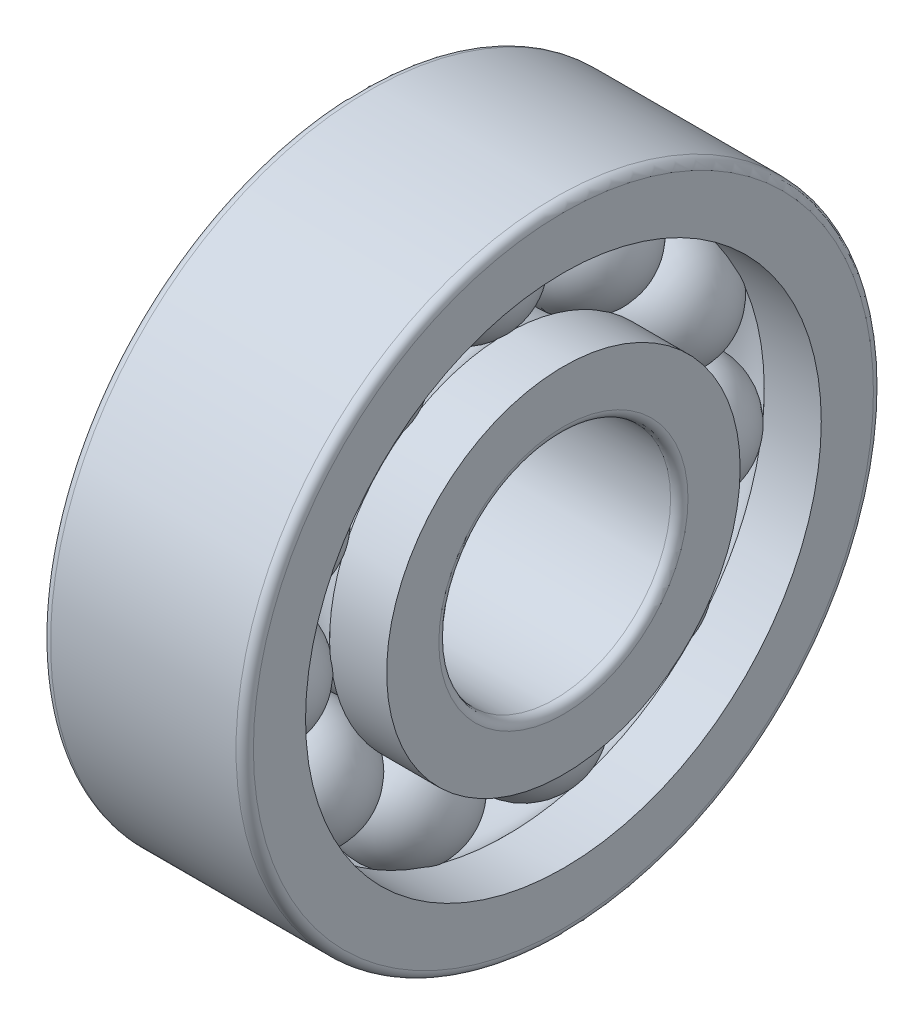
SolidWorks part; units mm, degrees
ref_plane "Plane1" through (0, 0, 0) normal (0, 0, 1) x (1, 0, 0)
ref_plane "Plane2" through (0, 0, 0) normal (0, 1, 0) x (1, 0, 0)
ref_plane "Plane3" through (0, 0, 0) normal (1, 0, 0) x (0, 0, -1)
revolve "InnerRace" add sketch "InnRacSke" angle 360 about L5 reverse direction yes
sketch "InnRacSke" plane through (0, 0, 0) normal (0, 0, 1) x (1, 0, 0)
  line L0 (-1.5315, 6.1) -> (-3.5, 6.1)
  line L1 (-3.5, 6.1) -> (-3.5, 4.3)
  line L2 (-3.2, 4) -> (3.2, 4)
  line L3 (3.5, 4.3) -> (3.5, 6.1)
  line L4 (3.5, 6.1) -> (1.5315, 6.1)
  line L5 (-20.6375, 0) -> (20.6375, 0) construction
  line L6 (0, 0) -> (0, 30) construction
  arc A0 (-3.5, 4.3) -> (-3.2, 4) centre (-3.2, 4.3) ccw
  arc A1 (3.2, 4) -> (3.5, 4.3) centre (3.2, 4.3) ccw
  arc A2 (1.5315, 6.1) -> (-1.5315, 6.1) centre (0, 7.5) cw
  dimension "Fillet_radius" = 0.3
  dimension "Ball_diameter" = 4.15
  dimension "ID" = 8
  dimension "OD" = 12.2
  dimension "Width" = 7
  dimension "BallCLRad" = 7.5
sketch "Clipboard" plane through (0, 0, 0) normal (0, 0, 1) x (1, 0, 0)
  line L0 (-10, 0) -> (10, 0) construction
  line L1 (0, 0) -> (21.9499, -4.2666)
  line L2 (0, 0) -> (7.4989, -0.1309)
  line L3 (0, 0) -> (22.3573, 0.3902)
  line L4 (0, 0) -> (-22.3573, -0.3902)
  dimension "BallCLRad" = 7.5
  dimension "Count" = 359
  dimension "Show_count" = 359
  dimension "Max_count" = 11
  dimension "Min_count" = 1
sketch "CagSpiSke" plane through (0, 0, 0) normal (0, 0, 1) x (1, 0, 0)
  line L0 (0.21, 7.15) -> (0.21, 7.85)
  line L1 (0.21, 7.85) -> (-0.21, 7.85)
  line L2 (-0.21, 7.85) -> (-0.21, 7.15)
  line L3 (-0.21, 7.15) -> (0.21, 7.15)
  line L4 (-20.6375, 0) -> (20.6375, 0) construction
  line L5 (0, 0) -> (0, 23.7692) construction
  dimension "Thickness" = 0.42
  dimension "OD" = 15.7
  dimension "ID" = 14.3
revolve "CageSpine" add sketch "CagSpiSke" angle 0.001 about L4 reverse direction yes
ref_axis "Axis1" through (-50, 0, 0) along (1, 0, 0)
sketch "CagBalSke" plane through (0, 0, 0) normal (0, 0, 1) x (1, 0, 0)
  line L0 (-2.31, 7.5) -> (2.31, 7.5)
  line L1 (-1.905, 7.5) -> (1.905, 7.5) construction
  line L2 (-10, 0) -> (10, 0) construction
  line L3 (0, 0) -> (0, 24) construction
  arc A0 (2.31, 7.5) -> (-2.31, 7.5) centre (0, 7.5) cw
  dimension "CageWallOD" = 4.62
  dimension "BallCLRad" = 7.5
revolve "CageBall" [suppressed] add sketch "CagBalSke" angle 360 about L1 reverse direction yes
pattern_circular "CageBalls" [suppressed] count 11 every 32.727 about axis through (-50, 0, 0) along (1, 0, 0)
sketch "CagTrmODSke" plane through (0, 0, 0) normal (0, 0, 1) x (1, 0, 0)
  line L0 (2.311, 7.85) -> (2.311, 9.811)
  line L1 (2.311, 9.811) -> (-2.311, 9.811)
  line L2 (-2.311, 9.811) -> (-2.311, 7.85)
  line L3 (-2.311, 7.85) -> (2.311, 7.85)
  line L4 (-20.6375, 0) -> (20.6375, 0) construction
  line L5 (0, 0) -> (0, 25) construction
  dimension "Width" = 4.622
  dimension "ID" = 15.7
  dimension "OD" = 19.622
revolve "CageTrimOD" [suppressed] cut sketch "CagTrmODSke" angle 360 about L4 reverse direction yes
sketch "CagTrmIDSke" plane through (0, 0, 0) normal (0, 0, 1) x (1, 0, 0)
  line L0 (2.311, 5.191) -> (2.311, 7.15)
  line L1 (2.311, 7.15) -> (-2.311, 7.15)
  line L2 (-2.311, 7.15) -> (-2.311, 5.191)
  line L3 (-2.311, 5.191) -> (2.311, 5.191)
  line L4 (-20.6375, 0) -> (20.6375, 0) construction
  line L5 (0, 0) -> (0, 25) construction
  dimension "ID" = 10.382
  dimension "OD" = 14.3
  dimension "Width" = 4.622
revolve "CageTrimID" [suppressed] cut sketch "CagTrmIDSke" angle 360 about L4 reverse direction yes
sketch "BalSimSke" plane through (0, 0, 0) normal (0, 0, 1) x (1, 0, 0)
  line L0 (-10, 0) -> (10, 0) construction
  line L1 (-10, 7.5) -> (10, 7.5) construction
  line L2 (0, 0) -> (0, 23) construction
  circle A0 centre (0, 7.5) radius 2.1
  dimension "Ball_diameter" = 4.2
  dimension "BallCLRad" = 7.5
revolve "BallsSimplified" [suppressed] add sketch "BalSimSke" angle 360 about L0
sketch "BalDetSke" plane through (0, 0, 0) normal (0, 0, 1) x (1, 0, 0)
  line L0 (-2.1, 7.5) -> (2.1, 7.5)
  line L1 (-1.905, 7.5) -> (1.905, 7.5) construction
  line L2 (0, 0) -> (0, 25) construction
  arc A0 (2.1, 7.5) -> (-2.1, 7.5) centre (0, 7.5) cw
  dimension "Ball_diameter" = 4.2
  dimension "BallCLRad" = 7.5
revolve "BallDetailed" add sketch "BalDetSke" angle 360 about L1 reverse direction yes
sketch "OutRacSke" plane through (0, 0, 0) normal (0, 0, 1) x (1, 0, 0)
  line L0 (-1.5315, 8.9) -> (-3.5, 8.9)
  line L1 (-3.5, 8.9) -> (-3.5, 10.7)
  line L2 (-3.2, 11) -> (3.2, 11)
  line L3 (3.5, 10.7) -> (3.5, 8.9)
  line L4 (3.5, 8.9) -> (1.5315, 8.9)
  line L5 (-20.6375, 0) -> (20.6375, 0) construction
  line L6 (0, 0) -> (0, 30) construction
  arc A0 (-3.5, 10.7) -> (-3.2, 11) centre (-3.2, 10.7) cw
  arc A1 (3.2, 11) -> (3.5, 10.7) centre (3.2, 10.7) cw
  arc A2 (1.5315, 8.9) -> (-1.5315, 8.9) centre (0, 7.5) ccw
  dimension "Fillet_radius" = 0.3
  dimension "Ball_diameter" = 4.15
  dimension "OD" = 22
  dimension "ID" = 17.8
  dimension "Width" = 7
  dimension "BallCLRad" = 7.5
revolve "OuterRace" add sketch "OutRacSke" angle 360 about L5 reverse direction yes
pattern_circular "BallsDetailed" count 11 every 32.727 about axis through (-50, 0, 0) along (1, 0, 0) of "BallDetailed"
equation "\"BallCLRad@Clipboard\" = ( \"OD@OutRacSke\" + \"ID@InnRacSke\" ) / 4"
equation "\"BallCLRad@BalSimSke\" = \"BallCLRad@Clipboard\""
equation "\"BallCLRad@BalDetSke\" = \"BallCLRad@Clipboard\""
equation "\"BallCLRad@InnRacSke\" = \"BallCLRad@Clipboard\""
equation "\"BallCLRad@OutRacSke\" = \"BallCLRad@Clipboard\""
equation "\"Ball_diameter@InnRacSke\" = \"Ball_diameter@BalDetSke\" - 0.05"
equation "\"Ball_diameter@OutRacSke\" = \"Ball_diameter@BalDetSke\" - 0.05"
equation "\"Ball_diameter@BalSimSke\" = \"Ball_diameter@BalDetSke\""
equation "\"Width@OutRacSke\" = \"Width@InnRacSke\""
equation "\"Fillet_radius@OutRacSke\" = \"Fillet_radius@InnRacSke\""
equation "\"Max_count@Clipboard\" = int( 3.14159265 / atn(( \"Ball_diameter@BalDetSke\" / 2) / sqr( \"BallCLRad@Clipboard\"  *  \"BallCLRad@Clipboard\" - ( \"Ball_diameter@BalDetSke\" / 2) *  ( \"Ball_diameter@BalDetSke\" / 2))))"
equation "\"Max_count@Clipboard\" = ((sgn( \"Max_count@Clipboard\" - \"Count@Clipboard\" )-1)*( \"Max_count@Clipboard\" - \"Count@Clipboard\" ))/-2+ \"Count@Clipboard\""
equation "\"Count@BallsDetailed\" = int( \"Show_count@Clipboard\" ) "
equation "\"Count@BallsDetailed\" = ((sgn( \"Count@BallsDetailed\" - \"Max_count@Clipboard\" )-1)*( \"Count@BallsDetailed\" - \"Max_count@Clipboard\" ))/-2+ \"Max_count@Clipboard\""
equation "\"Count@BallsDetailed\" = ((sgn( \"Count@BallsDetailed\" - \"Min_count@Clipboard\" )+1)*( \"Count@BallsDetailed\" - \"Min_count@Clipboard\"))/2 +\"Min_count@Clipboard\""
equation "\"Angle@BallsDetailed\" = 360.0 / \"Max_count@Clipboard\""
equation "\"BallCLRad@CagBalSke\" = \"BallCLRad@Clipboard\""
equation "\"Count@CageBalls\" = \"Count@BallsDetailed\""
equation "\"Angle@CageBalls\" = \"Angle@BallsDetailed\""
equation "\"Angle@CageSpine\" =  \"Angle@CageBalls\" * ( \"Count@CageBalls\" -1 + int( \"Count@CageBalls\" / \"Max_count@Clipboard\" ) )  + 0.001 -  int( \"Count@CageBalls\" / \"Max_count@Clipboard\" ) * 0.001"
equation "\"Angle@CageSpine\" =  \"Angle@CageSpine\" * int( \"Min_count@Clipboard\" / 2) + int(1 / \"Min_count@Clipboard\")  * 0.001"
equation "\"CageWallOD@CagBalSke\" =  \"Ball_diameter@BalDetSke\" * 1.1"
equation "\"Thickness@CagSpiSke\" =  \"Ball_diameter@BalDetSke\" * 0.1"
equation "\"OD@CagTrmODSke\" = \"BallCLRad@Clipboard\" * 2 + \"CageWallOD@CagBalSke\" + 0.002"
equation "\"ID@CagTrmODSke\" = \"BallCLRad@Clipboard\" * 2 + \"Ball_diameter@BalDetSke\" / 6"
equation "\"OD@CagTrmIDSke\" = \"BallCLRad@Clipboard\" * 2 - \"Ball_diameter@BalDetSke\" / 6"
equation "\"ID@CagTrmIDSke\" = \"BallCLRad@Clipboard\" * 2 - \"CageWallOD@CagBalSke\" + 0.002"
equation "\"OD@CagSpiSke\" = \"ID@CagTrmODSke\""
equation "\"ID@CagSpiSke\" = \"OD@CagTrmIDSke\""
equation "\"Width@CagTrmODSke\" = \"CageWallOD@CagBalSke\" + 0.002"
equation "\"Width@CagTrmIDSke\" = \"CageWallOD@CagBalSke\" + 0.002"
